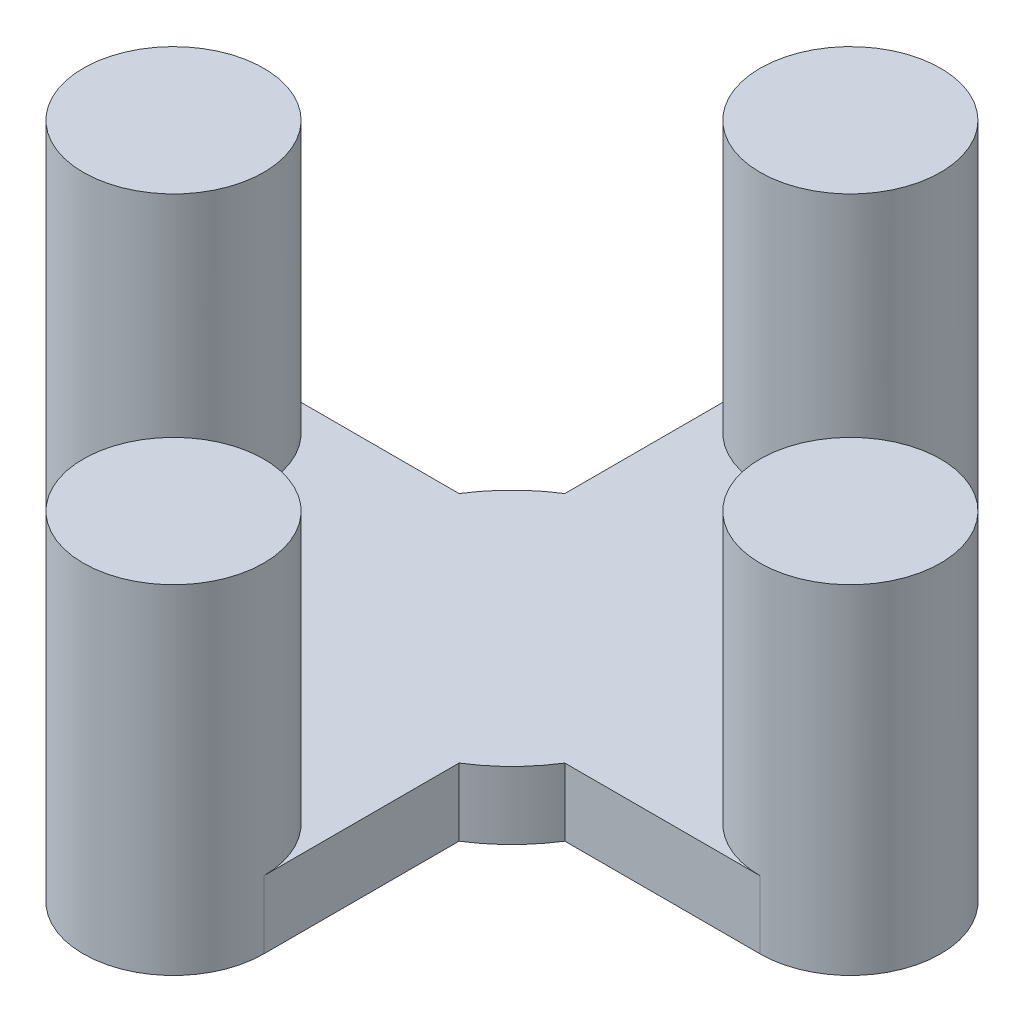
SolidWorks part; units mm, degrees
ref_plane "Front Plane" through (0, 0, 0) normal (0, 0, 1) x (1, 0, 0)
ref_plane "Top Plane" through (0, 0, 0) normal (0, 1, 0) x (1, 0, 0)
ref_plane "Right Plane" through (0, 0, 0) normal (1, 0, 0) x (0, 0, -1)
sketch "Sketch1" plane through (0, 0, 0) normal (0, 1, 0) x (1, 0, 0)
  line L3 (-15, 4) -> (-6.3443, 4)
  line L4 (-15, -4) -> (-6.3443, -4)
  line L6 (4, 15) -> (4, 6.3443)
  line L7 (-4, 15) -> (-4, 6.3443)
  line L8 (-4, -6.3443) -> (-4, -15)
  line L9 (6.3443, 4) -> (15, 4)
  line L10 (6.3443, -4) -> (15, -4)
  line L13 (4, -6.3443) -> (4, -15)
  arc A0 (-6.3443, -4) -> (-4, -6.3443) centre (0, 0) ccw
  arc A1 (-15, 4) -> (-15, -4) centre (-15, 0) ccw
  arc A2 (15, -4) -> (15, 4) centre (15, 0) ccw
  arc A3 (4, 15) -> (-4, 15) centre (0, 15) ccw
  arc A4 (-4, -15) -> (4, -15) centre (0, -15) ccw
  arc A5 (-4, 6.3443) -> (-6.3443, 4) centre (0, 0) ccw
  arc A6 (6.3443, 4) -> (4, 6.3443) centre (0, 0) ccw
  arc A7 (4, -6.3443) -> (6.3443, -4) centre (0, 0) ccw
  point P7 (0, 0)
  point P12 (0, 0)
  point P17 (0, 0)
  point P18 (0, 0)
  dimension "D1" = 15
  dimension "D4" = 4
  dimension "D5" = 4
  dimension "D2" = 30
  dimension "D3" = 30
extrude "Boss-Extrude1" add sketch "Sketch1" along normal blind 3
sketch "Sketch2" plane through (0, 3, 0) normal (0, 1, 0) x (1, 0, 0)
  circle A0 centre (-15, 0) radius 4
  circle A1 centre (15, 0) radius 4
  circle A2 centre (0, -15) radius 4
  circle A3 centre (0, 15) radius 4
extrude "Boss-Extrude2" add sketch "Sketch2" along normal blind 12
